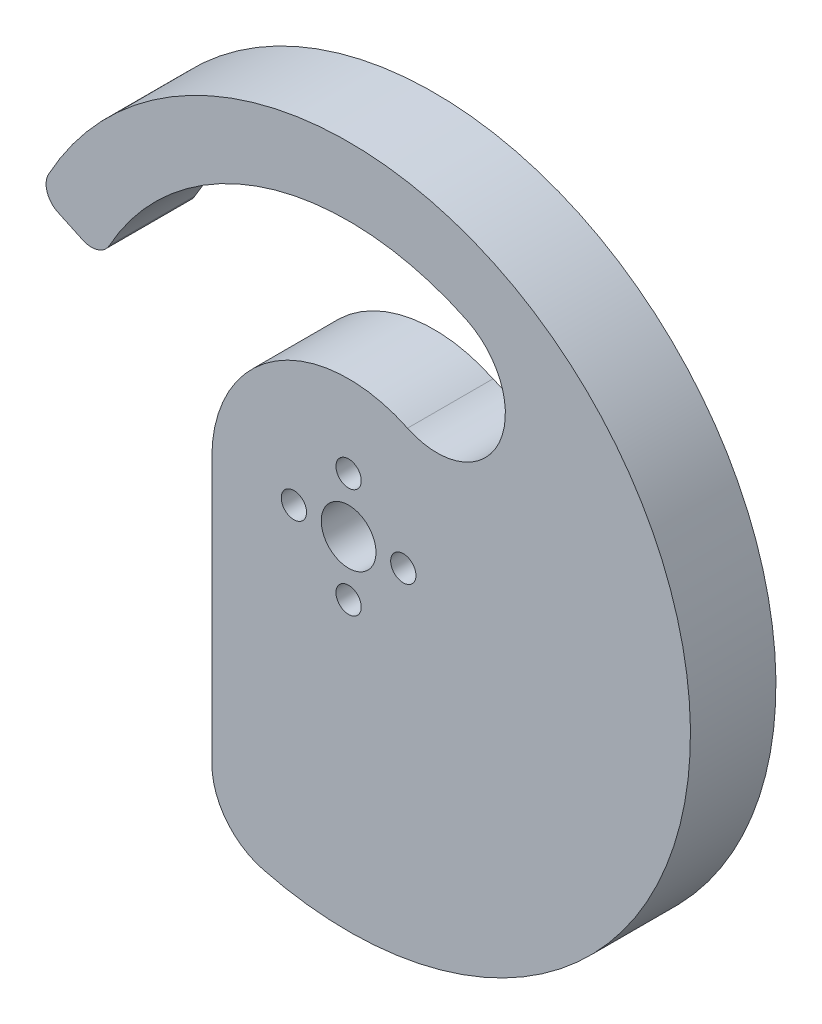
SolidWorks part; units mm, degrees
ref_plane "Front" through (0, 0, 0) normal (0, 0, 1) x (1, 0, 0)
ref_plane "Top" through (0, 0, 0) normal (0, 1, 0) x (1, 0, 0)
ref_plane "Right" through (0, 0, 0) normal (1, 0, 0) x (0, 0, -1)
sketch "Sketch1" plane through (0, 0, 0) normal (0, 0, 1) x (1, 0, 0)
  line L0 (0, 0) -> (0, 8) construction
  line L1 (0, 0) -> (-20, 0) construction
  line L3 (14.1421, 14.1421) -> (28.2843, 28.2843)
  line L4 (0, 0) -> (-45.3154, 21.1309) construction
  line L5 (-45.3154, 21.1309) -> (-36.2523, 16.9047)
  line L6 (-20, 0) -> (-20, -45.8258)
  arc A0 (-20, -45.8258) -> (-45.3154, 21.1309) centre (0, 0) ccw
  circle A1 centre (0, 0) radius 4
  circle A2 centre (0, 8) radius 1.85
  circle A3 centre (8, 0) radius 1.85
  circle A4 centre (0, -8) radius 1.85
  circle A5 centre (-8, 0) radius 1.85
  arc A6 (-20, 0) -> (14.1421, 14.1421) centre (0, 0) cw
  arc A7 (28.2843, 28.2843) -> (-36.2523, 16.9047) centre (0, 0) ccw
  point P15 (0, 0)
  dimension "D1" = 100
  dimension "D2" = 8
  dimension "D4" = 3.7
  dimension "D7" = 25
  dimension "D3" = 8
  dimension "D8" = 40
  dimension "D5" = 4
extrude "Boss-Extrude1" add sketch "Sketch1" along normal blind 12.5
fillet "Fillet1" radius 10 2 edges at (28.2843, 28.2843, 6.25) (14.1421, 14.1421, 6.25)
fillet "Fillet2" radius 3 2 edges at (-36.2523, 16.9047, 6.25) (-45.3154, 21.1309, 6.25)
fillet "Fillet3" radius 10 1 edges at (-20, -45.8258, 6.25)
